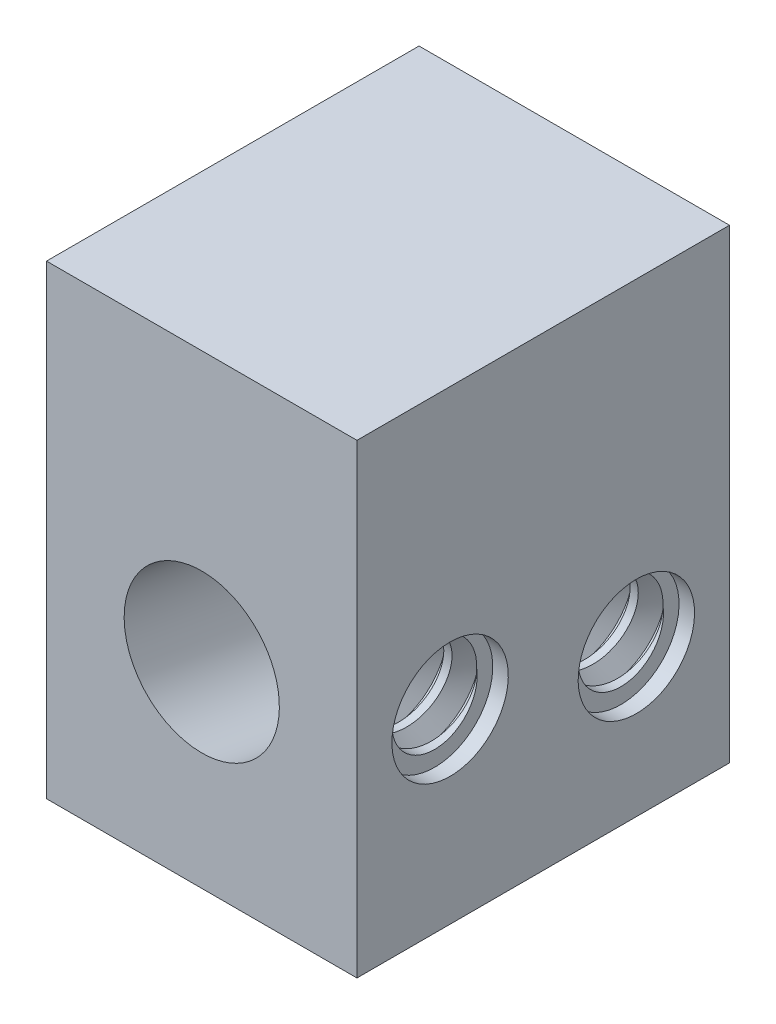
SolidWorks part; units mm, degrees
ref_plane "Front Plane" through (0, 0, 0) normal (0, 0, 1) x (1, 0, 0)
ref_plane "Top Plane" through (0, 0, 0) normal (0, 1, 0) x (1, 0, 0)
ref_plane "Right Plane" through (0, 0, 0) normal (1, 0, 0) x (0, 0, -1)
sketch "Sketch1" plane through (0, 0, 0) normal (0, 0, 1) x (1, 0, 0)
  line L1 (0, 0) -> (-20, 0)
  line L2 (0, 0) -> (0, -30)
  line L3 (0, -30) -> (-20, -30)
  line L4 (-20, 0) -> (-20, -30)
  dimension "D1" = 20
  dimension "D2" = 30
extrude "Boss-Extrude1" add sketch "Sketch1" along normal blind 24
sketch "Sketch25" plane through (0, 0, 0) normal (1, 0, 0) x (0, 0, -1)
  line L1 (0, -30) -> (0, 0) construction
  line L2 (1.8479, -16.5199) -> (0, -27)
  line L3 (0, -27) -> (0, -17)
  line L4 (1.8479, -16.5199) -> (0, -14)
  line L5 (0, -14) -> (0, -17)
  dimension "D1" = 10
  dimension "D2" = 10
  dimension "D3" = 3
  dimension "D4" = 3.1249
  dimension "D5" = 3
extrude "Boss-Extrude2" add sketch "Sketch25" against normal up to vertex (20 mm away) up to point (-20, 0, 0)
sketch "Sketch26" plane through (0, -0.8141, -4.6173) normal (0, -0.1736, -0.9848) x (-1, 0, 0)
  line L0 (20, -26.5898) -> (20, -15.948) construction
  line L1 (20, -26.5898) -> (0, -26.5898) construction
  circle A0 centre (10, -21.2689) radius 5
  point P4 (20, -21.2689)
  point P7 (10, -26.5898)
  dimension "D1" = 0
  dimension "D3" = 10
  dimension "D2" = 0
extrude "Cut-Extrude14" cut sketch "Sketch26" against normal blind 41
sketch "Sketch8" plane through (0, 0, 0) normal (0, 0, -1) x (-1, 0, 0)
  line L0 (0, 0) -> (20, 0) construction
  circle A0 centre (10, -9.5) radius 2
  point P4 (10, 0)
  dimension "D1" = 0
  dimension "D2" = 4
  dimension "D3" = 9.5
extrude "Cut-Extrude5" cut sketch "Sketch8" against normal blind 20
sketch "Sketch13" plane through (0, 0, 0) normal (1, 0, 0) x (0, 0, -1)
  line L0 (-24, -30) -> (0, -30) construction
  line L1 (0, -30) -> (0, -27) construction
  circle A0 centre (-6, -20.5) radius 2.75
  dimension "D1" = 9.5
  dimension "D2" = 5.5
  dimension "D3" = 6
extrude "Cut-Extrude8" cut sketch "Sketch13" against normal blind 10
thread "Thread3" pitch 2.1167 method cut profile "Thread Profile3" start angle 0, offset 0, length 10, pitch 2.1167, diameter 5.5
ref_plane "Plane3" through (0, -20.5, 8.75) normal (0, -1, 0) x (0, 0, 1)
sketch "Thread Profile3" plane through (0, -20.5, 8.75) normal (0, -1, 0) x (0, 0, 1)
  line L0 (0, 0) -> (0, 2.1167) construction
  line L1 (0, 0) -> (1.1457, 0.6615)
  line L2 (1.1457, 0.6615) -> (1.1457, 0.926)
  line L3 (1.1457, 0.926) -> (0, 1.5875)
  line L4 (1.1457, 0.7937) -> (0, 0.7937) construction
  line L11 (0, 0) -> (0, 1.5875)
  point P2 (0, 0)
  dimension "Pitch" = 2.1167
  dimension "Profile_Angle" = 60
  dimension "Profile_Land" = 0.2646
  dimension "Profile_Height" = 1.1457
sketch "Sketch16" plane through (0, 0, 0) normal (1, 0, 0) x (0, 0, -1)
  circle A0 centre (-6, -20.5) radius 3.75
  dimension "D1" = 7.5
extrude "Cut-Extrude9" cut sketch "Sketch16" against normal blind 1
sketch "Sketch19" plane through (0, 0, 0) normal (1, 0, 0) x (0, 0, -1)
  line L0 (-24, -30) -> (-24, 0) construction
  line L1 (-24, -30) -> (0, -30) construction
  circle A0 centre (-18, -18) radius 2.75
  dimension "D1" = 6
  dimension "D2" = 5.5
  dimension "D3" = 12
extrude "Cut-Extrude11" cut sketch "Sketch19" against normal blind 10
thread "Thread4" pitch 2.1167 method cut profile "Thread Profile4" start angle 0, offset 0, length 10, pitch 2.1167, diameter 5.5
ref_plane "Plane4" through (0, -18, 20.75) normal (0, -1, 0) x (0, 0, 1)
sketch "Thread Profile4" plane through (0, -18, 20.75) normal (0, -1, 0) x (0, 0, 1)
  line L0 (0, 0) -> (0, 2.1167) construction
  line L1 (0, 0) -> (1.1457, 0.6615)
  line L2 (1.1457, 0.6615) -> (1.1457, 0.926)
  line L3 (1.1457, 0.926) -> (0, 1.5875)
  line L4 (1.1457, 0.7937) -> (0, 0.7937) construction
  line L11 (0, 0) -> (0, 1.5875)
  point P2 (0, 0)
  dimension "Pitch" = 2.1167
  dimension "Profile_Angle" = 60
  dimension "Profile_Land" = 0.2646
  dimension "Profile_Height" = 1.1457
sketch "Sketch22" plane through (0, 0, 0) normal (1, 0, 0) x (0, 0, -1)
  circle A0 centre (-18, -18) radius 3.75
  dimension "D1" = 7.5
extrude "Cut-Extrude12" cut sketch "Sketch22" against normal blind 1
sketch "Sketch23" plane through (0, 0, 0) normal (0, 0, -1) x (-1, 0, 0)
  line L0 (0, -30) -> (0, -27) construction
  line L1 (5, -4) -> (2, -4)
  line L2 (5, -4) -> (5, -10)
  line L3 (5, -10) -> (2, -10)
  line L4 (2, -4) -> (2, -10)
  line L5 (0, 0) -> (20, 0) construction
  dimension "D1" = 2
  dimension "D2" = 3
  dimension "D3" = 6
  dimension "D4" = 4
extrude "Cut-Extrude13" cut sketch "Sketch23" against normal blind 14
sketch "Sketch27" plane through (0, 0, 0) normal (1, 0, 0) x (0, 0, -1)
  line L1 (0, -14) -> (5.6882, -14)
  line L2 (0, -14) -> (0, -27)
  line L3 (0, -27) -> (5.6882, -27)
  line L4 (5.6882, -14) -> (5.6882, -27)
  dimension "D1" = 0
extrude "Cut-Extrude15" cut sketch "Sketch27" against normal up to vertex (20 mm away) up to point (-20, -27, 0)
